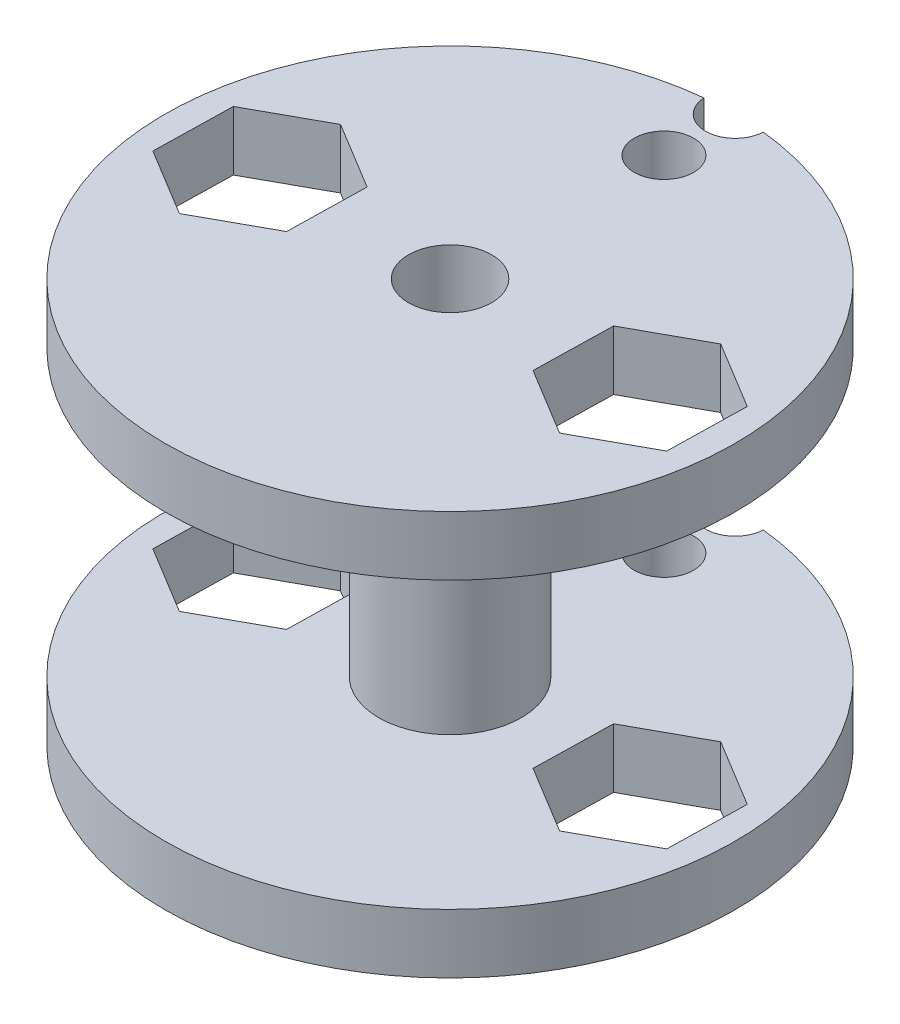
SolidWorks part; units mm, degrees
ref_plane "Front Plane" through (0, 0, 0) normal (0, 0, 1) x (1, 0, 0)
ref_plane "Top Plane" through (0, 0, 0) normal (0, 1, 0) x (1, 0, 0)
ref_plane "Right Plane" through (0, 0, 0) normal (1, 0, 0) x (0, 0, -1)
sketch "Sketch1" plane through (0, 0, 0) normal (0, 1, 0) x (1, 0, 0)
  circle A1 centre (0, 0) radius 12
  circle A2 centre (0, 0) radius 1.75
extrude "Boss-Extrude1" add sketch "Sketch1" along normal blind 2.5
sketch "Sketch2" plane through (0, 2.5, 0) normal (0, 1, 0) x (1, 0, 0)
  circle A0 centre (0, 0) radius 3
  circle A1 centre (0, 0) radius 1.75
sketch "Sketch3" plane through (0, 0, 0) normal (0, -1, 0) x (1, 0, 0)
  line L0 (-5.1613, 1.7213) -> (-8.0713, 3.319)
  line L1 (5.1613, -1.7213) -> (8.0713, -3.319)
  line L2 (8.0713, -3.319) -> (10.91, -1.5977)
  line L3 (10.91, -1.5977) -> (10.8387, 1.7213)
  line L4 (10.8387, 1.7213) -> (7.9287, 3.319)
  line L5 (7.9287, 3.319) -> (5.09, 1.5977)
  line L6 (5.09, 1.5977) -> (5.1613, -1.7213)
  line L7 (-8.0713, 3.319) -> (-10.91, 1.5977)
  line L8 (-10.91, 1.5977) -> (-10.8387, -1.7213)
  line L9 (-10.8387, -1.7213) -> (-7.9287, -3.319)
  line L10 (-7.9287, -3.319) -> (-5.09, -1.5977)
  line L11 (-5.09, -1.5977) -> (-5.1613, 1.7213)
  circle A0 centre (8, 0) radius 2.875 construction
  point P17 (0, 0)
  dimension "D2" = 8
  dimension "D1" = 2
extrude "Cut-Extrude3" cut sketch "Sketch3" against normal blind 2.5
sketch "Sketch4" plane through (0, 2.5, 0) normal (0, 1, 0) x (1, 0, 0)
  circle A0 centre (0, 9) radius 1.25
  circle A1 centre (0, 12) radius 1.25
  circle A2 centre (0, 0) radius 12 construction
  dimension "D1" = 9
extrude "Cut-Extrude4" cut sketch "Sketch4" against normal blind 5
sketch "Sketch5" plane through (0, 2.5, 0) normal (0, 1, 0) x (1, 0, 0)
  circle A0 centre (0, -16.2068) radius 3.1
extrude "Cut-Extrude5" [suppressed] cut sketch "Sketch5" along normal blind 2.5 from surface
extrude "Boss-Extrude2" add sketch "Sketch2" along normal blind 6
mirror "Mirror7" about plane through (0, 8.5, 0) normal (0, 1, 0) of bodies 107
